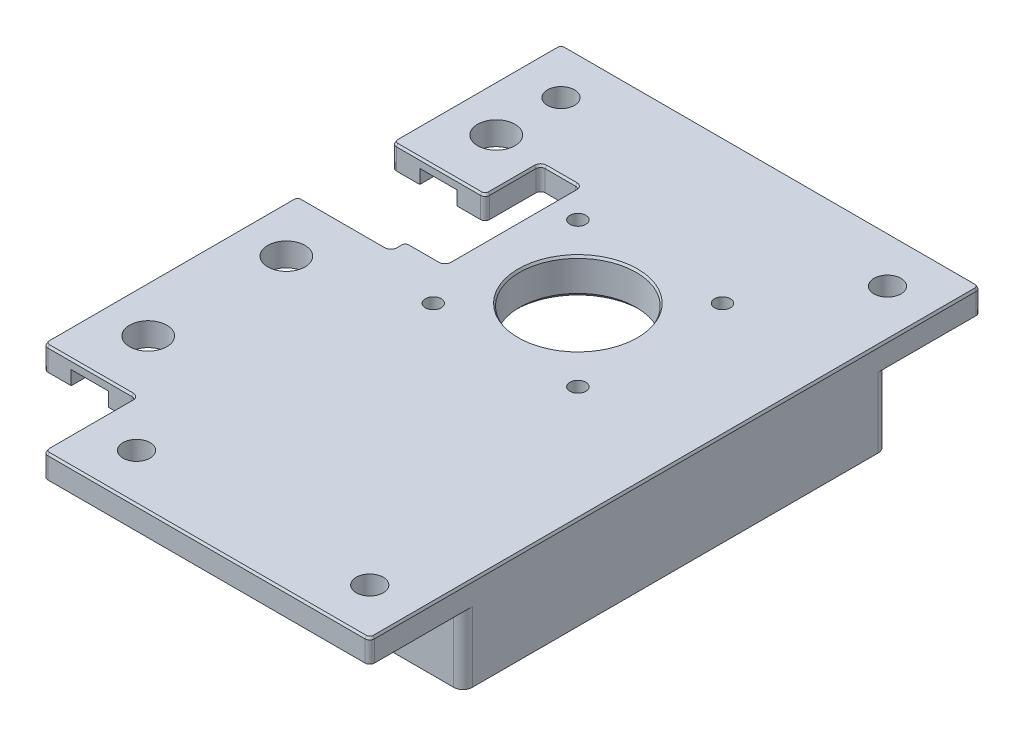
SolidWorks part; units mm, degrees
ref_plane "Front" through (0, 0, 0) normal (0, 0, 1) x (1, 0, 0)
ref_plane "Top" through (0, 0, 0) normal (0, 1, 0) x (1, 0, 0)
ref_plane "Right" through (0, 0, 0) normal (1, 0, 0) x (0, 0, -1)
sketch "Sketch1" plane through (0, 0, 0) normal (0, 1, 0) x (1, 0, 0)
  line L1 (0, 0) -> (90, 0)
  line L2 (0, 0) -> (0, 131)
  line L3 (0, 131) -> (90, 131)
  line L4 (90, 0) -> (90, 131)
  dimension "D1" = 90
  dimension "D2" = 131
extrude "Boss-Extrude1" add sketch "Sketch1" along normal blind 5
sketch "Sketch2" plane through (0, 5, 0) normal (0, 1, 0) x (1, 0, 0)
  line L0 (0, 94.625) -> (20, 94.625)
  line L1 (0, 131) -> (0, 0) construction
  line L2 (20, 94.625) -> (20, 91.625)
  line L3 (20, 91.625) -> (28.5, 91.625)
  line L4 (28.5, 91.625) -> (28.5, 77.625)
  line L5 (28.5, 77.625) -> (20, 77.625)
  line L6 (20, 77.625) -> (20, 74.625)
  line L7 (20, 74.625) -> (0, 74.625)
  line L8 (0, 74.625) -> (0, 94.625)
  line L9 (50, 84.625) -> (56.9971, 84.625) construction
  line L10 (0, 0) -> (20, 0)
  line L11 (0, 0) -> (0, 20)
  line L12 (0, 20) -> (20, 20)
  line L13 (20, 0) -> (20, 20)
  line L15 (90, 131) -> (0, 131) construction
  line L28 (28.5, 106.125) -> (28.5, 91.625) construction
  line L29 (34.5, 69.125) -> (65.5, 69.125) construction
  line L30 (34.5, 69.125) -> (34.5, 100.125) construction
  line L31 (34.5, 100.125) -> (65.5, 100.125) construction
  line L32 (65.5, 69.125) -> (65.5, 100.125) construction
  line L33 (34.5, 69.125) -> (65.5, 100.125) construction
  line L34 (34.5, 100.125) -> (65.5, 69.125) construction
  line L35 (71.5, 63.125) -> (28.5, 63.125) construction
  line L36 (71.5, 63.125) -> (71.5, 106.125) construction
  line L37 (71.5, 106.125) -> (28.5, 106.125) construction
  line L38 (28.5, 63.125) -> (28.5, 106.125) construction
  line L39 (71.5, 63.125) -> (28.5, 106.125) construction
  line L40 (71.5, 106.125) -> (28.5, 63.125) construction
  line L41 (28.5, 77.625) -> (28.5, 63.125) construction
  line L48 (32, 59.625) -> (68, 59.625) construction
  line L49 (32, 59.625) -> (32, 109.625) construction
  line L50 (32, 109.625) -> (68, 109.625) construction
  line L51 (68, 59.625) -> (68, 109.625) construction
  line L52 (32, 59.625) -> (68, 109.625) construction
  line L53 (32, 109.625) -> (68, 59.625) construction
  circle A0 centre (50, 84.625) radius 12.5
  circle A2 centre (65.5, 100.125) radius 1.7
  circle A3 centre (34.5, 100.125) radius 1.7
  circle A4 centre (65.5, 69.125) radius 1.7
  circle A5 centre (34.5, 69.125) radius 1.7
  circle A10 centre (32, 109.625) radius 1.7 construction
  circle A11 centre (68, 109.625) radius 1.7 construction
  circle A12 centre (68, 59.625) radius 1.7 construction
  circle A13 centre (32, 59.625) radius 1.7 construction
  point P14 (28.5, 84.625)
  point P54 (50, 84.625)
  dimension "D5" = 25
  dimension "D9" = 3.4
  dimension "D12" = 3.4
  dimension "D1" = 20
  dimension "D2" = 14
  dimension "D3" = 43
  dimension "D4" = 3
  dimension "D6" = 50
  dimension "D7" = 46.375
  dimension "D8" = 31
  dimension "D10" = 50
  dimension "D11" = 36
  dimension "D13" = 20
extrude "Cut-Extrude1" cut sketch "Sketch2" against normal up to next
hole_wizard "M5 Clearance Hole1" positions "Sketch3" profile "Sketch4" hole size "M5" standard "ANSI Metric" end condition through all
sketch "Sketch3" plane through (0, 5, 0) normal (0, 1, 0) x (1, 0, 0)
  line L0 (10, 20) -> (10, 131) construction
  line L1 (20, 20) -> (0, 20) construction
  line L2 (90, 131) -> (0, 131) construction
  line L5 (20, 10) -> (142.2662, 10) construction
  line L6 (20, 0) -> (20, 20) construction
  line L10 (0, 121) -> (90, 121) construction
  line L11 (0, 131) -> (0, 94.625) construction
  line L12 (90, 0) -> (90, 131) construction
  line L14 (20, 0) -> (90, 0) construction
  line L15 (0, 74.625) -> (0, 20) construction
  line L16 (90, 0) -> (90, 131) construction
  line L17 (90, 111) -> (0, 111) construction
  line L18 (90, 0) -> (90, 131) construction
  line L19 (20, 131) -> (20, 20) construction
  point P31 (10, 121)
  point P37 (80, 121)
  point P42 (30, 10)
  point P45 (80, 10)
  dimension "D1" = 10
  dimension "D2" = 10
  dimension "D3" = 10
  dimension "D4" = 10
  dimension "D5" = 10
  dimension "D6" = 10
  dimension "D7" = 20
sketch "Sketch4" plane through (80, 5, -10) normal (1, 0, 0) x (0, 0, 1)
  line L0 (0, 0) -> (0, 5)
  line L1 (0, 5) -> (2.9, 5)
  line L2 (2.9, 5) -> (2.9, 0)
  line L5 (2.9, 0) -> (0, 0)
  line L11 (0, -6.35) -> (0, 107.95) construction
  dimension "Thru Hole Dia." = 5.8
  dimension "Thru Hole Depth" = 5
sketch "Sketch6" plane through (0, 0, 0) normal (0, -1, 0) x (-1, 0, 0)
  line L0 (-20, 20) -> (0, 20) construction
  line L1 (0, 74.625) -> (-20, 74.625) construction
  line L2 (0, 74.625) -> (0, 20) construction
  line L3 (-20, 94.625) -> (0, 94.625) construction
  line L4 (0, 131) -> (0, 94.625) construction
  circle A0 centre (-10, 32.5) radius 4
  circle A1 centre (-10, 62.125) radius 4
  circle A2 centre (-10, 107.125) radius 4
  dimension "D2" = 8
  dimension "D1" = 12.5
  dimension "D3" = 12.5
  dimension "D4" = 10
  dimension "D5" = 10
  dimension "D6" = 12.5
  dimension "D7" = 10
extrude "Cut-Extrude2" cut sketch "Sketch6" against normal blind 10
other "Move Face1" flip direction yes face at (10, 2.5, -94.625) face at (10, 2.5, -74.625) offset 0.1 parameters "D1"=0.1
sketch "Sketch9" plane through (0, 0, 0) normal (0, -1, 0) x (1, 0, 0)
  line L0 (90, -111) -> (90, -20)
  line L1 (90, 0) -> (90, -131) construction
  line L2 (90, -20) -> (20, -20)
  line L3 (20, -20) -> (20, -74.525)
  line L4 (90, -111) -> (71, -111)
  line L5 (90, -131) -> (0, -131) construction
  line L6 (71, -111) -> (71, -106)
  line L7 (71, -106) -> (85, -106)
  line L8 (85, -106) -> (85, -25)
  line L9 (85, -25) -> (25, -25)
  line L10 (25, -25) -> (25, -74.525)
  line L11 (25, -74.525) -> (20, -74.525)
  line L12 (20, 0) -> (90, 0) construction
  line L13 (0, -74.525) -> (20, -74.525) construction
  line L14 (20, -74.525) -> (20, -77.625) construction
  dimension "D1" = 20
  dimension "D2" = 5
  dimension "D3" = 20
  dimension "D4" = 5
  dimension "D7" = 19
  dimension "D8" = 5
extrude "Boss-Extrude2" add sketch "Sketch9" along normal blind 15
fillet "Fillet4" radius 3 3 edges at (25, -7.5, -25) (85, -7.5, -25) (85, -7.5, -106)
fillet "Fillet5" radius 2 7 edges at (90, -7.5, -20) (90, -7.5, -111) (71, -7.5, -111) (71, -7.5, -106) (20, -7.5, -20) (25, -7.5, -74.525) (20, -7.5, -74.525)
ref_plane "Plane1" through (10, 0, 0) normal (-1, 0, 0) x (0, 0, 1)
sketch "Sketch10" plane through (10, 0, 0) normal (-1, 0, 0) x (0, 0, 1)
  line L0 (-74.525, 0) -> (-74.525, 3)
  line L1 (-28, 0) -> (-103, 0) construction
  line L2 (-74.525, 0) -> (-74.525, 5) construction
  line L3 (-74.525, 3) -> (-71.525, 0)
  line L5 (-71.525, 0) -> (-74.525, 0)
  line L6 (-97.725, 0) -> (-94.725, 0)
  line L8 (-94.725, 0) -> (-94.725, 3)
  line L10 (-94.725, 3) -> (-97.725, 0)
  line L11 (-20, 0) -> (-23, 0)
  line L13 (-20, 0) -> (0, 0) construction
  line L16 (-20, 0) -> (-20, 3)
  line L17 (-20, 0) -> (-20, 5) construction
  line L18 (-20, 3) -> (-23, 0)
  line L21 (-94.725, 0) -> (-94.725, 5) construction
  dimension "D1" = 45
  dimension "D2" = 3
extrude "Cut-Extrude5" cut sketch "Sketch10" against normal blind 4 and the other way blind 4
sketch "Sketch11" plane through (0, 5, 0) normal (0, 1, 0) x (1, 0, 0)
  line L5 (28.5, 77.625) -> (28.5, 91.625) construction
  line L6 (20, 91.625) -> (28.5, 91.625)
  line L7 (20, 91.625) -> (20, 106.625)
  line L8 (20, 106.625) -> (28.5, 106.625)
  line L9 (28.5, 91.625) -> (28.5, 106.625)
  dimension "D1" = 15
extrude "Cut-Extrude6" cut sketch "Sketch11" against normal through all
fillet "Fillet6" radius 1 14 edges at (28.5, 2.5, -77.625) (90, 2.5, 0) (90, 2.5, -131) (0, 2.5, -131) (0, 2.5, -94.725) (20, 2.5, -74.525) (20, 2.5, -77.625) (0, 2.5, -74.525) (0, 2.5, -20) (20, 2.5, 0) (20, 2.5, -20) (28.5, 2.5, -106.625) (20, 2.5, -94.725) (20, 2.5, -106.625)
sketch "Sketch15" plane through (0, 0, 0) normal (0, -1, 0) x (1, 0, 0)
  line L0 (29.5, -100.125) -> (29.5, -69.125)
  line L1 (34.5, -64.125) -> (65.5, -64.125)
  line L2 (70.5, -69.125) -> (70.5, -100.125)
  line L3 (34.5, -105.125) -> (65.5, -105.125)
  circle A0 centre (65.5, -100.125) radius 1.7 construction
  circle A1 centre (34.5, -100.125) radius 1.7 construction
  circle A2 centre (65.5, -69.125) radius 1.7 construction
  circle A3 centre (34.5, -69.125) radius 1.7 construction
  circle A4 centre (65.5, -100.125) radius 1.7
  circle A5 centre (34.5, -100.125) radius 1.7
  circle A6 centre (65.5, -69.125) radius 1.7
  circle A7 centre (34.5, -69.125) radius 1.7
  circle A8 centre (50, -84.625) radius 12.5 construction
  circle A9 centre (50, -84.625) radius 12.5
  circle A10 centre (34.5, -69.125) radius 5 construction
  circle A11 centre (34.5, -100.125) radius 5 construction
  circle A12 centre (65.5, -100.125) radius 5 construction
  circle A13 centre (65.5, -69.125) radius 5 construction
  arc A14 (29.5, -100.125) -> (34.5, -105.125) centre (34.5, -100.125) ccw
  arc A15 (29.5, -69.125) -> (34.5, -64.125) centre (34.5, -69.125) cw
  arc A16 (65.5, -64.125) -> (70.5, -69.125) centre (65.5, -69.125) cw
  arc A17 (70.5, -100.125) -> (65.5, -105.125) centre (65.5, -100.125) cw
  dimension "D1" = 10
extrude "Boss-Extrude3" add sketch "Sketch15" along normal blind 3
chamfer "Chamfer1" distance 1 angle 45 9 edges at (50, -3, -97.125) (70.5, 0, -84.625) (69.0355, 0, -65.5895) (69.0355, 0, -103.6605) (50, 0, -64.125) (50, 0, -105.125) (30.9645, 0, -65.5895) (30.9645, 0, -103.6605) (29.5, 0, -84.625)
chamfer "Printability Chamfer" distance 0.5 angle 30 29 edges at (24.25, 5, -77.625) (20.2929, 5, -77.3321) (28.2071, 5, -77.9179) (20, 5, -76.075) (28.5, 5, -92.125) (19.7071, 5, -74.8179) (28.2071, 5, -106.3321) (10, 5, -74.525) (24.25, 5, -106.625) (0.2929, 5, -74.2321) (20.2929, 5, -106.3321) (0, 5, -47.2625) (20, 5, -100.675) (0.2929, 5, -20.2929) (19.7071, 5, -95.0179) (10, 5, -20) (10, 5, -94.725) (19.7071, 5, -19.7071) (0.2929, 5, -95.0179) (20, 5, -10) (0, 5, -112.8625) (20.2929, 5, -0.2929) (0.2929, 5, -130.7071) (55, 5, 0) (45, 5, -131) (89.7071, 5, -0.2929) (89.7071, 5, -130.7071) (90, 5, -65.5) (50, 5, -72.125) first distance on face at (24.25, 2.5, -77.625) first distance on face at (20.3964, 2.5, -77.2286) first distance on face at (28.1036, 2.5, -78.0214) first distance on face at (20, 2.5, -76.075) first distance on face at (28.5, 2, -93.725) first distance on face at (19.6036, 2.5, -74.9214) first distance on face at (28.1036, 2.5, -106.2286) first distance on face at (10, 2, -74.525) first distance on face at (24.25, 2.5, -106.625) first distance on face at (0.3964, 2.5, -74.1286) first distance on face at (20.3964, 2.5, -106.2286) first distance on face at (0, 2.5, -47.2625) first distance on face at (20, 2.5, -100.675) first distance on face at (0.3964, 2.5, -20.3964) first distance on face at (19.6036, 2.5, -95.1214) first distance on face at (10, 2, -20) first distance on face at (10, 2, -94.725) first distance on face at (19.6036, 2.5, -19.6036) first distance on face at (0.3964, 2.5, -95.1214) first distance on face at (20, 2.5, -10) first distance on face at (0, 2.5, -112.8625) first distance on face at (20.3964, 2.5, -0.3964) first distance on face at (0.3964, 2.5, -130.6036) first distance on face at (55, 2.5, 0) first distance on face at (45, 2.5, -131) first distance on face at (89.6036, 2.5, -0.3964) first distance on face at (89.6036, 2.5, -130.6036) first distance on face at (90, -2.5, -65.5) first distance on face at (50, -2, -97.125)
mirror "Mirror1" [suppressed] of bodies 114 108
delete or keep bodies "Body-Delete/Keep 1" [suppressed] type delete bodies bodies 114
sketch "Sketch12" plane through (0, 5, 0) normal (1, 0, 0) x (0, -1, 0)
  line L0 (4.4, 131) -> (4.4, 94.725) construction
  line L4 (5, 131) -> (0.5, 131) construction
  line L5 (5, 130) -> (5, 95.725) construction
  line L6 (0.5, 94.725) -> (5, 94.725) construction
  text T0 "LZP-04" font "Century Gothic" height in points 12
  dimension "D1" = 0.6
extrude "Left Part Num" cut sketch "Sketch12" along normal blind 0.4
sketch "Sketch13" [suppressed] plane through (180, -175, 0) normal (-1, 0, 0) x (0, 1, 0)
  line L0 (175.6, 94.725) -> (175.6, 131) construction
  line L4 (175, 131) -> (179.5, 131) construction
  line L5 (179.5, 94.725) -> (175, 94.725) construction
  line L6 (175, 130) -> (175, 95.725) construction
  text T0 "RZP-03" font "Century Gothic" height in points 12
  dimension "D1" = 0.6
extrude "Right Part Num" [suppressed] cut sketch "Sketch13" along normal blind 0.4
equation "\"D3@Sketch6\"=\"D1@Sketch6\""
equation "\"D6@Sketch6\"=\"D1@Sketch6\""
equation "\"D8@Sketch9\"=\"D4@Sketch9\""
equation "\"D2@Sketch9\"=\"D4@Sketch9\""
